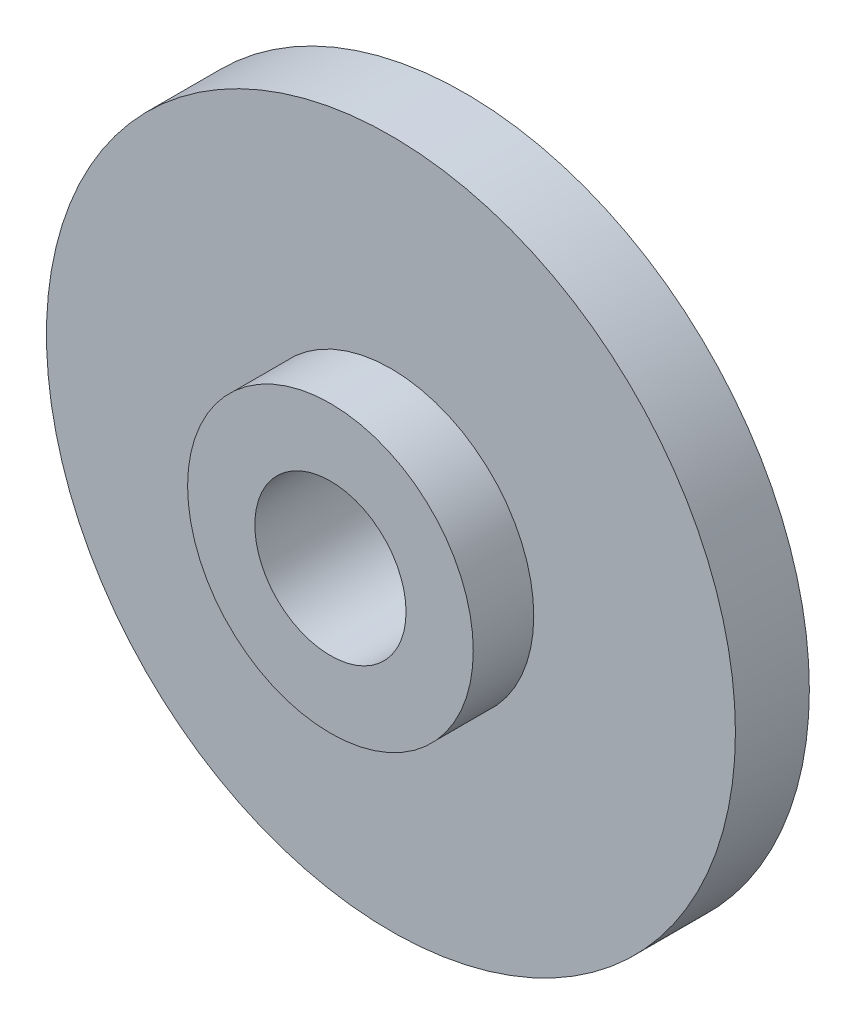
SolidWorks part; units mm, degrees
ref_plane "Front Plane" through (0, 0, 0) normal (0, 0, 1) x (1, 0, 0)
ref_plane "Top Plane" through (0, 0, 0) normal (0, 1, 0) x (1, 0, 0)
ref_plane "Right Plane" through (0, 0, 0) normal (1, 0, 0) x (0, 0, -1)
sketch "Sketch1" plane through (0, 0, 0) normal (0, 0, 1) x (1, 0, 0)
  circle A0 centre (0, 0) radius 10.25
  circle A1 centre (0, 0) radius 4.25
  circle A2 centre (0, 0) radius 2.25
  dimension "D1" = 20.5
  dimension "D2" = 8.5
  dimension "D3" = 2
extrude "Boss-Extrude1" add sketch "Sketch1" along normal blind 2.2 contours A0 A1 region at (-9.9601, 0, 0)
extrude "Boss-Extrude2" add sketch "Sketch1<3>" along normal blind 4 contours A1 A2 region at (-4.1298, 0, 0)
sketch "Sketch1<3>" plane through (0, 0, 0) normal (0, 0, 1) x (1, 0, 0) same geometry as "Sketch1"
